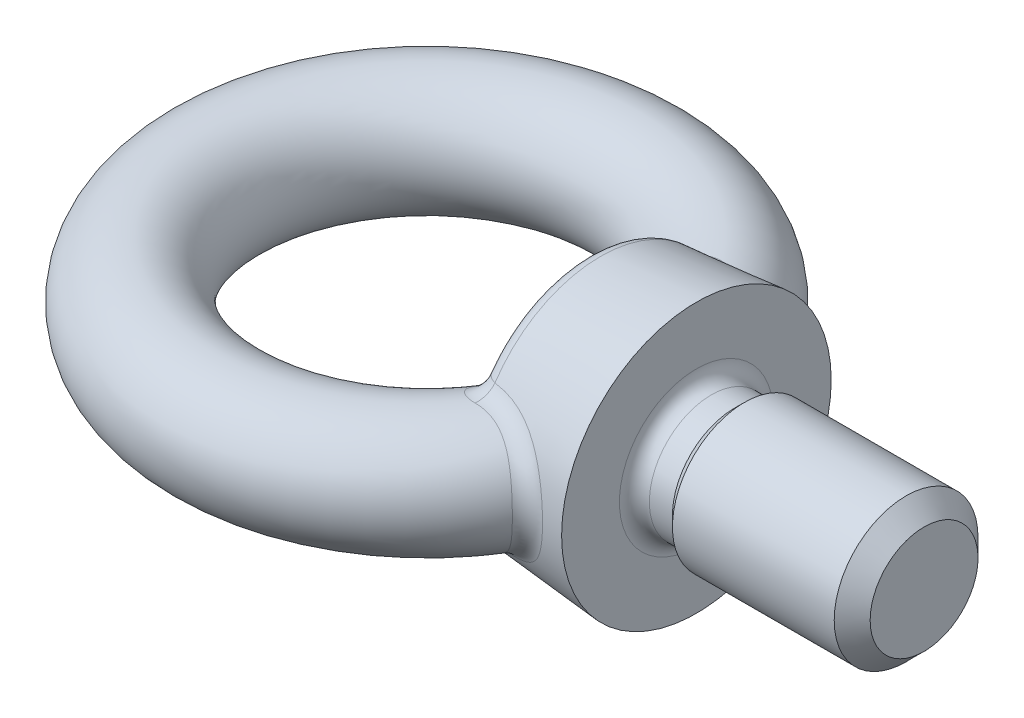
SolidWorks part; units mm, degrees
ref_plane "Front Plane" through (0, 0, 0) normal (0, 0, 1) x (1, 0, 0)
ref_plane "Top Plane" through (0, 0, 0) normal (0, 1, 0) x (1, 0, 0)
ref_plane "Right Plane" through (0, 0, 0) normal (1, 0, 0) x (0, 0, -1)
sketch "BaseBodySke" plane through (0, 0, 0) normal (0, 0, 1) x (1, 0, 0)
  line L0 (-107.4075, 0) -> (214.0904, 0) construction
  line L1 (0, 0) -> (0, 10.352)
  line L2 (8, 12) -> (6.352, 10.352)
  line L3 (6.352, 10.352) -> (0, 10.352)
  line L4 (8, 12) -> (38, 12)
  line L5 (38, 12) -> (38, 0)
  line L6 (38, 0) -> (0, 0)
  line L7 (8, 24.2031) -> (8, -17.9005) construction
  line L8 (34.0602, 10.352) -> (57.5082, 10.352) construction
  line L9 (35, 13.8049) -> (35, -14.5195) construction
  dimension "D2" = 45
  dimension "Thread_length" = 30
  dimension "Length" = 38
  dimension "Advance" = 3
revolve "BaseBody" add sketch "BaseBodySke" angle 360 about L6
cosmetic thread "ThreadCosmetic" [suppressed] parameters "Thread_length"=30, "Thread_minor"=20.704
sketch "HeadBaseSke" plane through (0, 0, 0) normal (0, 0, 1) x (1, 0, 0)
  line L0 (0, 0) -> (-36.296, 0) construction
  line L1 (-18, 20.9252) -> (0, 22.5)
  line L2 (-20, 0) -> (0, 0)
  line L3 (-45, 33.5024) -> (-45, -15.844) construction
  line L4 (0, 22.5) -> (0, 0)
  line L5 (-20, 0) -> (-18, 20.9252)
  dimension "Head_height" = 18
  dimension "D2" = 5
revolve "HeadBase" add sketch "HeadBaseSke" angle 360 about L0
sketch "RingSke" plane through (0, 0, 0) normal (0, 0, 1) x (1, 0, 0)
  line L0 (-45, 45.564) -> (-45, -44.2909) construction
  line L1 (0, 29.3194) -> (0, -32.008) construction
  circle A0 centre (-10, 0) radius 10
  dimension "D1" = 45
revolve "Ring" add sketch "RingSke" angle 360 about L0
sketch "FlatEndSke" plane through (0, 0, 0) normal (0, 0, 1) x (1, 0, 0)
  line L0 (35, 12) -> (38, 12)
  line L1 (38, 12) -> (38, 9)
  line L2 (38, 9) -> (35, 12)
  line L3 (38, -12) -> (38, 12) construction
  line L5 (0, 0) -> (89.7899, 0) construction
  dimension "D1" = 45
revolve "FlatEnd" cut sketch "FlatEndSke" angle 360 about L5
sketch "CutEndSke" plane through (38, 0, 0) normal (1, 0, 0) x (0, 0, -1)
  circle A0 centre (0, 0) radius 12 construction
  circle A1 centre (0, 0) radius 12
extrude "CutEnd" [suppressed] cut sketch "CutEndSke" against normal blind 3
dome "RoundEnd" [suppressed] faces to dome 1 distance 3 parameters "D1"=3
fillet "Fillet1" radius 2.4 2 edges at (-18, 20.9252, 0) (-18, -20.9252, 0)
fillet "Fillet2" radius 3.6 8 edges at (-17.4293, 9.7808, 17.9838) (-19.811, 1.9468, -0.3451) (-17.5159, 9.7551, -17.9021) (-5.8247, 1.3824, -21.9469) (-17.4293, -9.7808, -17.9838) (-19.811, -1.9468, 0.3451) (-17.5159, -9.7551, 17.9021) (-5.8247, -1.3824, 21.9469)
fillet "Fillet" radius 2.5 1 edges at (0, 0, -10.352)
sketch "ThdSchSke" plane through (0, 0, 0) normal (0, 0, 1) x (1, 0, 0)
  line L0 (0, 0) -> (89.8666, 0) construction
  line L1 (38, -27.1828) -> (38, 30.5493) construction
  line L2 (35, 10.352) -> (34.0485, 12)
  line L3 (34.0485, 12) -> (34.0485, 13.9029)
  line L4 (34.0485, 13.9029) -> (35.9515, 13.9029)
  line L5 (35.9515, 13.9029) -> (35.9515, 12)
  line L6 (35.9515, 12) -> (35, 10.352)
  dimension "Length" = 38
  dimension "Advance" = 3
  dimension "D1" = 20.704
  dimension "D2" = 24
revolve "ThreadSchematic" [suppressed] cut sketch "ThdSchSke" angle 360 about L0
pattern_linear "ThdSchPat" [suppressed] count 10 spacing 3 along (-1, 0, 0) of bodies 105
equation "\"Thread_length@BaseBodySke\" = \"Length@BaseBodySke\" - \"Slot_width@BaseBodySke\""
equation "\"Thread_minor@ThreadCosmetic\" = \"Minor_dia@BaseBodySke\""
equation "\"Thread_length@ThreadCosmetic\" = \"Thread_length@BaseBodySke\""
equation "\"D1@RingSke\" = \"Center_height@HeadBaseSke\""
equation "\"D1@CutEnd\" = \"Chamfer_width@FlatEndSke\""
equation "\"D1@RoundEnd\" = \"Chamfer_width@FlatEndSke\""
equation "\"D1@Fillet1\" = \"Diameter@BaseBodySke\"/10"
equation "\"D1@Fillet2\" = \"D1@Fillet1\"*1.5"
equation "\"Length@ThdSchSke\" = \"Length@BaseBodySke\""
equation "\"Advance@ThdSchSke\" = \"Advance@BaseBodySke\""
equation "\"D2@ThdSchSke\" = \"Diameter@BaseBodySke\""
equation "\"D1@ThdSchSke\" = \"Minor_dia@BaseBodySke\""
equation "\"D3@ThdSchPat\" = \"Advance@BaseBodySke\""
equation "\"D1@ThdSchPat\" =  int( \"Thread_length@BaseBodySke\" / \"Advance@BaseBodySke\" ) "
